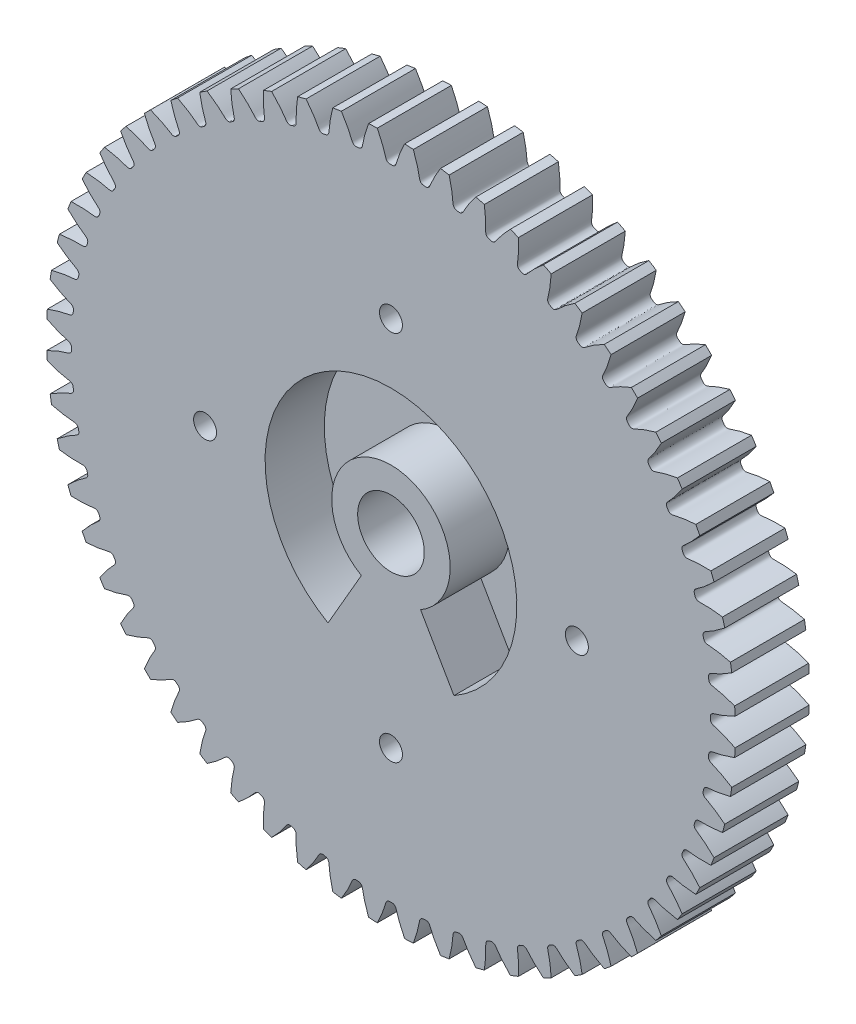
SolidWorks part; units mm, degrees
ref_plane "Front Plane" through (0, 0, 0) normal (0, 0, 1) x (1, 0, 0)
ref_plane "Top Plane" through (0, 0, 0) normal (0, 1, 0) x (1, 0, 0)
ref_plane "Right Plane" through (0, 0, 0) normal (1, 0, 0) x (0, 0, -1)
ref_axis "Axis1" through (0, 0, 5.5) along (0, 0, -1)
sketch "SketchRevolveSpurAssembly01Gear" plane through (0, 0, 0) normal (1, 0, 0) x (0, 0, -1)
  line L0 (0, 0) -> (1, 0) construction
  line L1 (-5, 0) -> (-5, 46.5)
  line L2 (-5, 46.5) -> (5, 46.5)
  line L3 (5, 46.5) -> (5, 0)
  line L4 (5, 0) -> (-5, 0)
  dimension "Side1" = 5
  dimension "OutsideRadius" = 46.5
  dimension "Side2" = 5
revolve "SpurAssembly01Gear" add sketch "SketchRevolveSpurAssembly01Gear" angle 360 about L0
sketch "SketchToothSpurAssembly01Gear" plane through (0, 0, 0) normal (0, 0, 1) x (1, 0, 0)
  arc A0 (46.5369, 1.8824) -> (46.5369, -1.8824) centre (0, 0) cw
  spline S0 degree 3 poles (46.5369, -1.8824) (46.4106, -1.8178) (46.2223, -1.724) (45.9725, -1.6049) (45.7913, -1.5209) (45.614, -1.4411) (45.4406, -1.3655) (45.2713, -1.2938) (45.1061, -1.2261) (44.945, -1.1621) (44.7882, -1.1018) (44.6356, -1.0452) (44.4874, -0.992) (44.3436, -0.9422) (44.2043, -0.8957) (44.0695, -0.8523) (43.9392, -0.8123) (43.7554, -0.7565) (43.5912, -0.7185) (43.4569, -0.6604) (43.397, -0.6284) (43.3333, -0.5856) (43.2647, -0.5249) (43.195, -0.4361) (43.14, -0.3154) (43.1191, -0.1635) (43.1282, 0) (43.1191, 0.1635) (43.14, 0.3154) (43.195, 0.4361) (43.2647, 0.5249) (43.3333, 0.5856) (43.397, 0.6284) (43.4569, 0.6604) (43.5912, 0.7185) (43.7554, 0.7565) (43.9392, 0.8123) (44.0695, 0.8523) (44.2043, 0.8957) (44.3436, 0.9422) (44.4874, 0.992) (44.6356, 1.0452) (44.7882, 1.1018) (44.945, 1.1621) (45.1061, 1.2261) (45.2713, 1.2938) (45.4406, 1.3655) (45.614, 1.4411) (45.7913, 1.5209) (45.9725, 1.6049) (46.2223, 1.724) (46.4106, 1.8178) (46.5369, 1.8824) knots 0 0 0 0 0.051766 0.076686 0.100963 0.124598 0.147592 0.169943 0.191651 0.212718 0.233143 0.252925 0.272065 0.290563 0.308419 0.325633 0.342204 0.358133 0.395729 0.403327 0.411415 0.420483 0.431261 0.444675 0.461387 0.478965 0.5 0.521035 0.538613 0.555325 0.568739 0.579517 0.588585 0.596673 0.604271 0.641867 0.657796 0.674367 0.691581 0.709437 0.727935 0.747075 0.766857 0.787282 0.808349 0.830057 0.852408 0.875402 0.899037 0.923314 0.948234 1 1 1 1
extrude "ToothExtrudeCutSpurAssembly01Gear" cut sketch "SketchToothSpurAssembly01Gear" against normal blind 5 and the other way blind 5
pattern_circular "PatternSpurAssembly01Gear" count 60 over 360 about axis through (0, 0, 5.5) along (0, 0, -1) of "ToothExtrudeCutSpurAssembly01Gear"
sketch "AuxiliarySketchSpurAssembly01Gear" plane through (0, 0, 0) normal (0, 0, 1) x (1, 0, 0)
  circle A0 centre (0, 0) radius 45 construction
  circle A1 centre (0, 0) radius 42.2862 construction
  circle A2 centre (0, 0) radius 43.6372 construction
  circle A3 centre (0, 0) radius 46.5 construction
  circle A4 centre (0, 0) radius 43.125 construction
  dimension "PitchDiameter" = 90
  dimension "BaseDiameter" = 84.5723
  dimension "FormDiameter" = 87.2745
  dimension "MajorDiameter" = 93
  dimension "MinorDiameter" = 86.25
sketch "Sketch3" plane through (0, 0, 5) normal (0, 0, 1) x (1, 0, 0)
  circle A0 centre (0, 0) radius 4
sketch "Sketch4" plane through (0, 0, 5) normal (0, 0, 1) x (1, 0, 0)
  line L0 (0, 0) -> (-9.5, -16.4545) construction
  line L1 (0, 0) -> (9.5, -16.4545) construction
  line L2 (-4, -6.9282) -> (-8.5, -14.7224)
  line L3 (4, -6.9282) -> (8.5, -14.7224)
  arc A1 (8.5, -14.7224) -> (-8.5, -14.7224) centre (0, 0) ccw
  arc A2 (4, -6.9282) -> (-4, -6.9282) centre (0, 0) ccw
sketch "Sketch5" plane through (0, 0, -5) normal (0, 0, -1) x (-1, 0, 0)
  circle A0 centre (0, 0) radius 4.5
extrude "Cut-Extrude2" cut sketch "Sketch5" against normal blind 18
sketch "Sketch6" plane through (0, 0, -5) normal (0, 0, -1) x (-1, 0, 0)
  circle A0 centre (25.1, 0) radius 1.55
extrude "Cut-Extrude3" cut sketch "Sketch6" against normal blind 10
pattern_circular "CirPattern2" count 4 over 360 about axis through (0, 0, 5.5) along (0, 0, -1) of "Cut-Extrude3"
extrude "Cut-Extrude4" cut sketch "Sketch4" against normal blind 8
sketch "Sketch7" plane through (0, 0, -5) normal (0, 0, -1) x (-1, 0, 0)
  circle A0 centre (-25.1, 0) radius 3.5
  circle A1 centre (0, 25.1) radius 3.5
  circle A2 centre (25.1, 0) radius 3.5
  circle A3 centre (0, -25.1) radius 3.5
  point P12 (0, 0)
  dimension "D1" = 4
extrude "Cut-Extrude5" cut sketch "Sketch7" against normal blind 3
